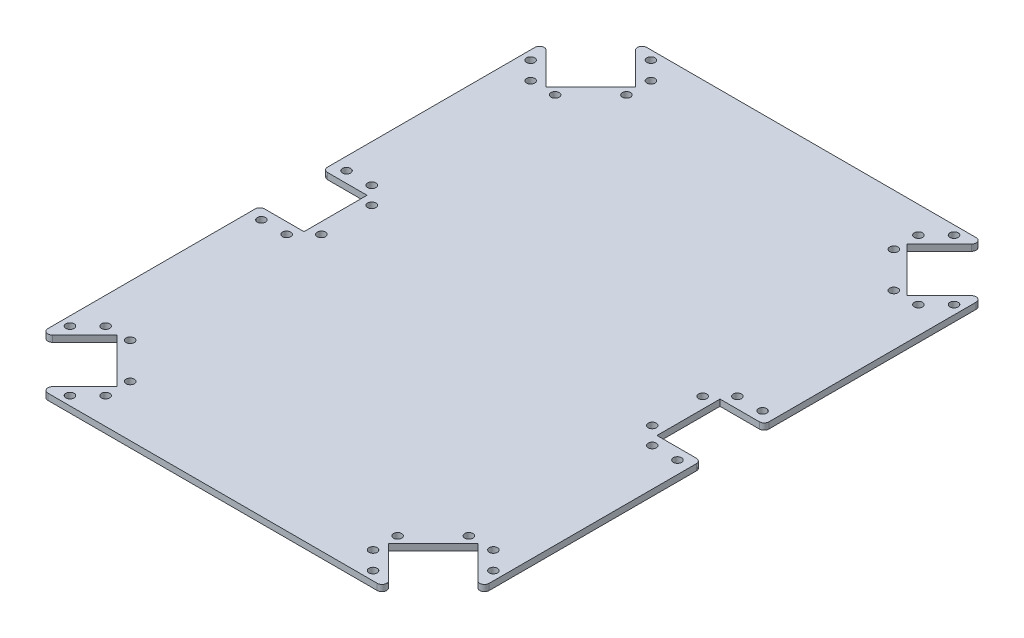
SolidWorks part; units mm, degrees
ref_plane "Front Plane" through (0, 0, 0) normal (0, 0, 1) x (1, 0, 0)
ref_plane "Top Plane" through (0, 0, 0) normal (0, 1, 0) x (1, 0, 0)
ref_plane "Right Plane" through (0, 0, 0) normal (1, 0, 0) x (0, 0, -1)
sketch "Sketch2" plane through (0, 0, 0) normal (0, 1, 0) x (1, 0, 0)
  line L0 (-70, 0) -> (70, 0) construction
  line L1 (-70, 95) -> (70, 95)
  line L2 (-70, 95) -> (-70, -95)
  line L3 (-70, -95) -> (70, -95)
  line L4 (70, 95) -> (70, -95)
  line L5 (70, 95) -> (0, 25) construction
  line L7 (0, 95) -> (0, -95) construction
  line L8 (42.4228, 78.7365) -> (38.5337, 82.6256) construction
  line L9 (38.5337, 82.6256) -> (42.4228, 86.5147) construction
  line L10 (42.4228, 86.5147) -> (48.0797, 92.1716) construction
  line L11 (48.0797, 92.1716) -> (50.9081, 95) construction
  circle A5 centre (42.4228, 78.7365) radius 1.3
  circle A6 centre (42.4228, 86.5147) radius 1.3
  circle A7 centre (48.0797, 92.1716) radius 1.3
  circle A8 centre (66, 13.5) radius 1.3
  circle A9 centre (58, 13.5) radius 1.3
  circle A10 centre (52.5, 8) radius 1.3
  circle A11 centre (52.5, -8) radius 1.3
  circle A12 centre (58, -13.5) radius 1.3
  circle A13 centre (66, -13.5) radius 1.3
  circle A14 centre (67.1716, 73.0797) radius 1.3
  circle A15 centre (61.5147, 67.4228) radius 1.3
  circle A16 centre (53.7365, 67.4228) radius 1.3
  circle A17 centre (67.1716, -73.0797) radius 1.3
  circle A18 centre (61.5147, -67.4228) radius 1.3
  circle A19 centre (53.7365, -67.4228) radius 1.3
  circle A20 centre (48.0797, -92.1716) radius 1.3
  circle A21 centre (42.4228, -86.5147) radius 1.3
  circle A22 centre (42.4228, -78.7365) radius 1.3
  circle A23 centre (-48.0797, 92.1716) radius 1.3
  circle A24 centre (-42.4228, 86.5147) radius 1.3
  circle A25 centre (-42.4228, 78.7365) radius 1.3
  circle A26 centre (-67.1716, 73.0797) radius 1.3
  circle A27 centre (-61.5147, 67.4228) radius 1.3
  circle A28 centre (-53.7365, 67.4228) radius 1.3
  circle A29 centre (-67.1716, -73.0797) radius 1.3
  circle A30 centre (-61.5147, -67.4228) radius 1.3
  circle A31 centre (-53.7365, -67.4228) radius 1.3
  circle A32 centre (-42.4228, -78.7365) radius 1.3
  circle A33 centre (-42.4228, -86.5147) radius 1.3
  circle A34 centre (-48.0797, -92.1716) radius 1.3
  circle A35 centre (-52.5, -8) radius 1.3
  circle A36 centre (-58, -13.5) radius 1.3
  circle A37 centre (-66, -13.5) radius 1.3
  circle A38 centre (-66, 13.5) radius 1.3
  circle A39 centre (-58, 13.5) radius 1.3
  circle A40 centre (-52.5, 8) radius 1.3
  point P0 (0, 0)
  point P27 (0, 0)
  dimension "D6" = 5.5
  dimension "D10" = 8
  dimension "D11" = 5.5
  dimension "D2" = 2.6
  dimension "D3" = 8
  dimension "D4" = 4
  dimension "D5" = 5.5
  dimension "D7" = 45
  dimension "D8" = 140
  dimension "D9" = 190
  dimension "D12" = 5.5
  dimension "D13" = 8
  dimension "D14" = 4
  dimension "D15" = 8
extrude "Boss-Extrude1" add sketch "Sketch2" along normal blind 2
sketch "Sketch3" plane through (0, 2, 0) normal (0, 1, 0) x (1, 0, 0)
  line L0 (0, -95) -> (0, 95) construction
  line L1 (-70, -95) -> (70, -95) construction
  line L2 (70, 95) -> (-70, 95) construction
  line L3 (-70, 0) -> (70, 0) construction
  line L4 (-70, 95) -> (-70, -95) construction
  line L5 (70, -95) -> (70, 95) construction
  line L6 (70, 95) -> (0, 25) construction
  line L7 (70, -10) -> (56, -10)
  line L8 (70, -10) -> (70, 10)
  line L9 (70, 10) -> (56, 10)
  line L10 (56, -10) -> (56, 10)
  line L11 (55.8579, 95) -> (43.1299, 82.2721)
  line L12 (43.1299, 82.2721) -> (57.2721, 68.1299)
  line L13 (57.2721, 68.1299) -> (70, 80.8579)
  line L14 (70, 80.8579) -> (70, 95)
  line L15 (70, 95) -> (55.8579, 95)
  line L16 (70, -80.8579) -> (70, -95)
  line L17 (57.2721, -68.1299) -> (70, -80.8579)
  line L18 (43.1299, -82.2721) -> (57.2721, -68.1299)
  line L19 (55.8579, -95) -> (43.1299, -82.2721)
  line L20 (70, -95) -> (55.8579, -95)
  line L21 (-70, 80.8579) -> (-70, 95)
  line L22 (-57.2721, 68.1299) -> (-70, 80.8579)
  line L23 (-43.1299, 82.2721) -> (-57.2721, 68.1299)
  line L24 (-55.8579, 95) -> (-43.1299, 82.2721)
  line L25 (-70, 95) -> (-55.8579, 95)
  line L26 (-70, 10) -> (-56, 10)
  line L27 (-56, -10) -> (-56, 10)
  line L28 (-70, -10) -> (-56, -10)
  line L29 (-70, -10) -> (-70, 10)
  line L30 (-57.2721, -68.1299) -> (-70, -80.8579)
  line L31 (-43.1299, -82.2721) -> (-57.2721, -68.1299)
  line L32 (-55.8579, -95) -> (-43.1299, -82.2721)
  line L33 (-70, -95) -> (-55.8579, -95)
  line L34 (-70, -80.8579) -> (-70, -95)
  dimension "D1" = 10
  dimension "D2" = 20
  dimension "D3" = 14
  dimension "D4" = 45
  dimension "D5" = 18
  dimension "D6" = 20
  dimension "D7" = 10
extrude "Cut-Extrude1" cut sketch "Sketch3" against normal up to surface (2 mm away) up to face at (0, 0, 0)
fillet "Fillet1" radius 1.5 12 edges at (-70, 1, 10) (-70, 1, -10) (-70, 1, 80.8579) (-55.8579, 1, 95) (55.8579, 1, 95) (70, 1, 80.8579) (70, 1, 10) (70, 1, -10) (70, 1, -80.8579) (55.8579, 1, -95) (-70, 1, -80.8579) (-55.8579, 1, -95)
